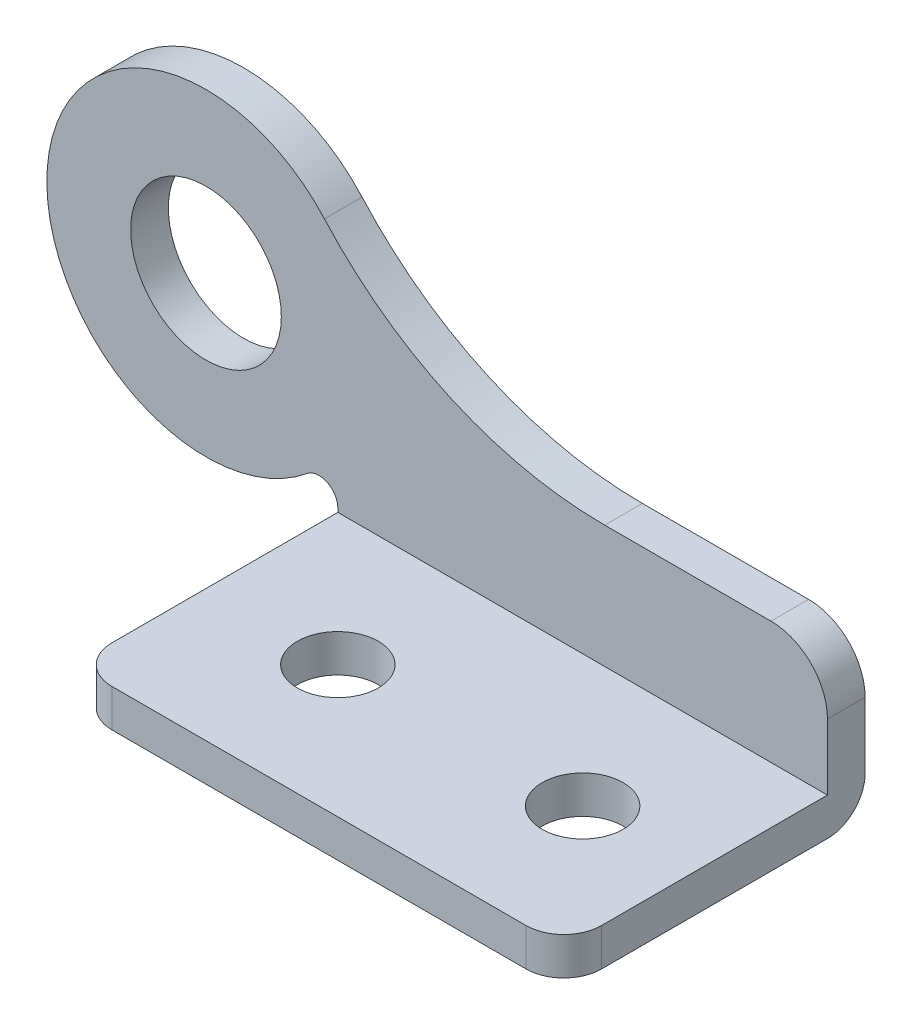
SolidWorks part; units mm, degrees
material "6061 合金"
ref_plane "前视基准面" through (0, 0, 0) normal (0, 0, 1) x (1, 0, 0)
ref_plane "上视基准面" through (0, 0, 0) normal (0, 1, 0) x (1, 0, 0)
ref_plane "右视基准面" through (0, 0, 0) normal (1, 0, 0) x (0, 0, -1)
sketch "草图1" plane through (0, 0, 0) normal (0, 0, 1) x (1, 0, 0)
  line L0 (-5.4584, -21.0602) -> (-5.4584, -21.2593)
  line L1 (-5.4584, -21.2593) -> (20.5416, -21.2593)
  line L2 (20.5416, -21.2593) -> (20.5416, -17.7593)
  line L3 (17.5416, -14.7593) -> (8.7172, -14.7593)
  line L4 (20.5416, -21.2593) -> (20.5416, -23.2593)
  line L5 (18.5416, -23.2593) -> (-3.4584, -23.2593)
  line L6 (-5.4584, -23.2593) -> (-3.4584, -23.2593)
  line L7 (-5.4584, -21.2593) -> (-5.4584, -23.2593)
  line L8 (18.5416, -23.2593) -> (20.5416, -23.2593)
  arc A0 (-5.4584, -21.0602) -> (-7.0933, -20.2876) centre (-6.4584, -21.0602) ccw
  arc A1 (20.5416, -17.7593) -> (17.5416, -14.7593) centre (17.5416, -17.7593) ccw
  arc A2 (-6.169, -8.1161) -> (8.7172, -14.7593) centre (8.7172, 5.2407) ccw
  arc A3 (-6.169, -8.1161) -> (-7.0933, -20.2876) centre (-12.4584, -13.7593) ccw
  arc A4 (-12.4584, -9.7593) -> (-12.4584, -17.7593) centre (-12.4584, -13.7593) ccw
  arc A5 (-12.4584, -17.7593) -> (-12.4584, -9.7593) centre (-12.4584, -13.7593) ccw
extrude "凸台-拉伸1" add sketch "草图1" along normal blind 2 contours A2 A3 A0 L0 L1 L2 A1 L3 A5 A4 | L5 L8 L4 L1 L7 L6 region at (-2.6372, -15.7191, 0) region at (7.5416, -22.2593, 0)
sketch "草图2" plane through (0, -23.2593, 0) normal (0, -1, 0) x (1, 0, 0)
  line L0 (18.5416, 16) -> (-3.4584, 16)
  line L3 (20.5416, 0) -> (-5.4584, 0)
  line L4 (-5.4584, 2) -> (-5.4584, 0)
  line L5 (-5.4584, 14) -> (-5.4584, 2)
  line L6 (1.5416, 9) -> (14.5416, 9) construction
  line L7 (18.5416, 14) -> (20.5416, 14) construction
  line L8 (18.5416, 14) -> (18.5416, 16) construction
  line L9 (20.5416, 0) -> (-5.4584, 0) construction
  line L10 (20.5416, 14) -> (20.5416, 0)
  line L11 (20.5416, 2) -> (20.5416, 0) construction
  arc A0 (16.6916, 9) -> (12.7243, 10.1488) centre (14.5416, 9) ccw
  arc A1 (12.7243, 10.1488) -> (16.6916, 9) centre (14.5416, 9) ccw
  circle A2 centre (1.5416, 9) radius 2.15
  arc A4 (-3.4584, 16) -> (-5.4584, 14) centre (-3.4584, 14) ccw
  arc A5 (20.5416, 14) -> (18.5416, 16) centre (18.5416, 14) ccw
  point P4 (10.5399, 10.1488)
  point P6 (-3.4584, 16)
  point P9 (-0.6084, 8.763)
  point P14 (0, 0)
  point P18 (0, 0)
  point P21 (0, 0)
  point P24 (2.7575, 7.2268)
  dimension "D3" = 2.15
  dimension "D4" = 2.15
  dimension "D8" = 2
  dimension "D9" = 2
  dimension "D1" = 26
  dimension "D2" = 9
  dimension "D5" = 13
  dimension "D6" = 7
  dimension "D7" = 16
extrude "凸台-拉伸2" add sketch "草图2" against normal blind 2
fillet "圆角1" radius 2 1 edges at (7.5416, -23.2593, 0)
